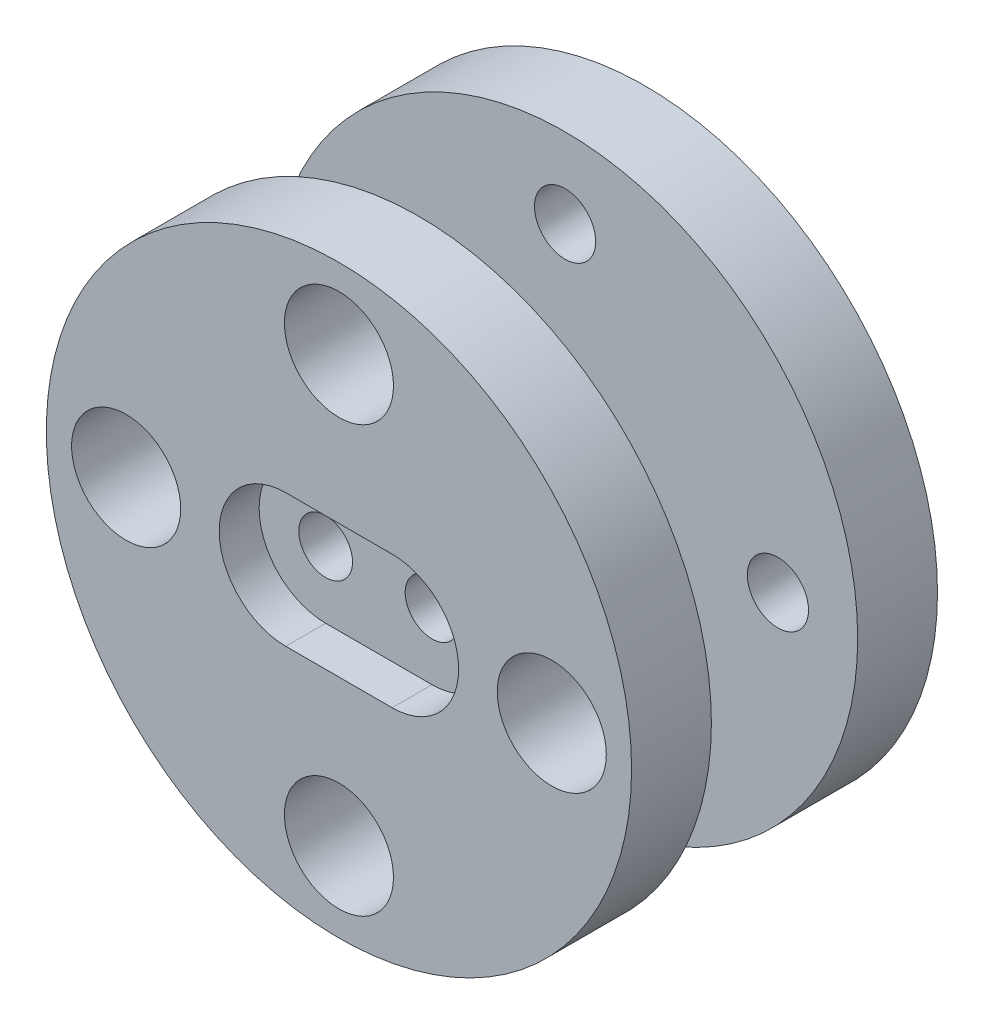
SolidWorks part; units mm, degrees
material "ﾎﾟﾘｵｷｼﾒﾁﾚﾝ(POM)ｱｾﾀｰﾙ共重合体"
ref_plane "正面" through (0, 0, 0) normal (0, 0, 1) x (1, 0, 0)
ref_plane "平面" through (0, 0, 0) normal (0, 1, 0) x (1, 0, 0)
ref_plane "右側面" through (0, 0, 0) normal (1, 0, 0) x (0, 0, -1)
sketch "ｽｹｯﾁ1" plane through (0, 0, 0) normal (0, 0, 1) x (1, 0, 0)
  line L0 (0, 0) -> (-8, 0) construction
  circle A0 centre (-8, 0) radius 1.15
  circle A1 centre (0, 8) radius 1.15
  circle A2 centre (8, 0) radius 1.15
  circle A3 centre (0, -8) radius 1.15
  circle A4 centre (0, 0) radius 11
  circle A5 centre (0, 0) radius 3 construction
  point P13 (0, 0)
  dimension "D1" = 2.3
  dimension "D4" = 22
  dimension "D5" = 6
  dimension "D2" = 8
  dimension "D3" = 4
extrude "ﾎﾞｽ - 押し出し1" add sketch "ｽｹｯﾁ1" along normal blind 3
sketch "ｽｹｯﾁ2" plane through (0, 0, 3) normal (0, 0, 1) x (1, 0, 0)
  circle A0 centre (0, 0) radius 3
  dimension "D1" = 6
extrude "ﾎﾞｽ - 押し出し2" add sketch "ｽｹｯﾁ2" along normal blind 5.5 separate body
sketch "ｽｹｯﾁ3" plane through (0, 0, 8.5) normal (0, 0, 1) x (1, 0, 0)
  circle A1 centre (0, 0) radius 11
  circle A2 centre (0, 0) radius 11
  circle A10 centre (-8, 0) radius 2.05
  circle A11 centre (0, 8) radius 2.05
  circle A12 centre (8, 0) radius 2.05
  circle A13 centre (0, -8) radius 2.05
  point P14 (0, 0)
  dimension "D2" = 4.1
  dimension "D1" = 0
  dimension "D3" = 4
extrude "ﾎﾞｽ - 押し出し3" add sketch "ｽｹｯﾁ3" along normal blind 3 separate body
sketch "ｽｹｯﾁ8" plane through (0, 0, 11.5) normal (0, 0, 1) x (1, 0, 0)
  line L0 (0, 3) -> (0, 0) construction
  line L1 (0, 0) -> (-2, 0) construction
  circle A0 centre (0, 0) radius 3 construction
  circle A1 centre (-2, 0) radius 1.01
  circle A2 centre (2, 0) radius 1.01
  dimension "D1" = 6
  dimension "D2" = 2
  dimension "D3" = 2.02
extrude "ｶｯﾄ - 押し出し4" cut sketch "ｽｹｯﾁ8" against normal up to surface (8.5 mm away) up to face at (9.15, 0, 3)
sketch "ｽｹｯﾁ9" plane through (0, 0, 3) normal (0, 0, 1) x (1, 0, 0)
  circle A0 centre (-2, 0) radius 0.8
  circle A1 centre (2, 0) radius 0.8
  dimension "D1" = 1.6
extrude "ｶｯﾄ - 押し出し5" cut sketch "ｽｹｯﾁ9" against normal up to surface (3 mm away) up to face at (11, 0, 0)
sketch "ｽｹｯﾁ11" plane through (0, 0, 11.5) normal (0, 0, 1) x (1, 0, 0)
  line L0 (-2, 0) -> (2, 0) construction
  line L1 (-2, 2.5) -> (2, 2.5)
  line L2 (-2, -2.5) -> (2, -2.5)
  arc A0 (-2, 2.5) -> (-2, -2.5) centre (-2, 0) ccw
  arc A1 (2, -2.5) -> (2, 2.5) centre (2, 0) ccw
  point P4 (0, 0)
  dimension "D1" = 2.5
extrude "ｶｯﾄ - 押し出し6" cut sketch "ｽｹｯﾁ11" against normal offset from surface (1.5 mm away) 10 up to face at (-1.2, 0, 0)
